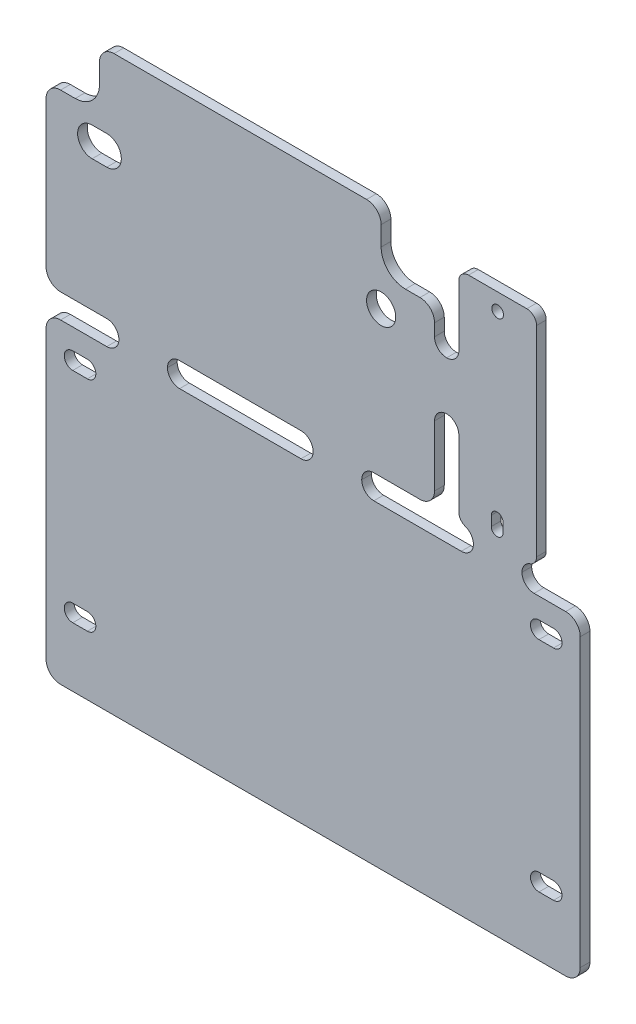
SolidWorks part; units mm, degrees
ref_plane "正面" through (0, 0, 0) normal (0, 0, 1) x (1, 0, 0)
ref_plane "平面" through (0, 0, 0) normal (0, 1, 0) x (1, 0, 0)
ref_plane "右側面" through (0, 0, 0) normal (1, 0, 0) x (0, 0, -1)
sketch "ｽｹｯﾁ1" plane through (0, 0, 0) normal (0, 0, 1) x (1, 0, 0)
  line L0 (-49.5, 24.75) -> (-46.5, 24.75)
  line L1 (55, 32.5) -> (-55, 32.5)
  line L2 (55, 32.5) -> (55, -32.5)
  line L3 (55, -32.5) -> (-55, -32.5)
  line L4 (-55, 32.5) -> (-55, -32.5)
  line L5 (55, 32.5) -> (-55, -32.5) construction
  line L6 (55, -32.5) -> (-55, 32.5) construction
  line L7 (-46.5, 28.25) -> (-49.5, 28.25)
  line L8 (-46.5, 28.25) -> (-46.5, 24.75) construction
  line L10 (-49.5, 28.25) -> (-49.5, 24.75) construction
  line L11 (-46.5, 28.25) -> (-49.5, 24.75) construction
  line L12 (-46.5, 24.75) -> (-49.5, 28.25) construction
  line L13 (-55, 4) -> (55, 4) construction
  line L14 (0, 32.5) -> (0, -32.5) construction
  line L15 (-46.5, -20.25) -> (-49.5, -20.25)
  line L16 (-49.5, -16.75) -> (-46.5, -16.75)
  line L17 (46.5, -20.25) -> (49.5, -20.25)
  line L18 (49.5, -16.75) -> (46.5, -16.75)
  line L19 (46.5, 28.25) -> (49.5, 28.25)
  line L20 (49.5, 24.75) -> (46.5, 24.75)
  arc A2 (-49.5, 28.25) -> (-49.5, 24.75) centre (-49.5, 26.5) ccw
  arc A3 (-46.5, 28.25) -> (-46.5, 24.75) centre (-46.5, 26.5) cw
  arc A4 (-49.5, -20.25) -> (-49.5, -16.75) centre (-49.5, -18.5) cw
  arc A5 (-46.5, -20.25) -> (-46.5, -16.75) centre (-46.5, -18.5) ccw
  arc A6 (46.5, -20.25) -> (46.5, -16.75) centre (46.5, -18.5) cw
  arc A7 (49.5, -20.25) -> (49.5, -16.75) centre (49.5, -18.5) ccw
  arc A8 (49.5, 28.25) -> (49.5, 24.75) centre (49.5, 26.5) cw
  arc A9 (46.5, 28.25) -> (46.5, 24.75) centre (46.5, 26.5) ccw
  point P0 (0, 0)
  point P6 (-48, 26.5)
  dimension "D3" = 3.5
  dimension "D4" = 3
  dimension "D1" = 65
  dimension "D2" = 110
  dimension "D5" = 6
  dimension "D6" = 7
  dimension "D7" = 22.5
extrude "ﾎﾞｽ - 押し出し1" add sketch "ｽｹｯﾁ1" along normal blind 2
fillet "ﾌｨﾚｯﾄ1" radius 3 4 edges at (55, 32.5, 1) (55, -32.5, 1) (-55, -32.5, 1) (-55, 32.5, 1)
sketch "ｽｹｯﾁ2" plane through (0, 0, 2) normal (0, 0, 1) x (1, 0, 0)
  line L0 (-45.5, 64.5) -> (-42.5, 64.5)
  line L2 (-55, 85.5) -> (-55, 37.5) construction
  line L3 (-55, 37.5) -> (25, 37.5) construction
  line L4 (25, 85.5) -> (25, 37.5) construction
  line L5 (-55, 85.5) -> (25, 37.5) construction
  line L6 (-55, 37.5) -> (25, 85.5) construction
  line L7 (-45.5, 70.5) -> (-42.5, 70.5)
  line L8 (-45.5, 70.5) -> (-45.5, 64.5) construction
  line L10 (-42.5, 70.5) -> (-42.5, 64.5) construction
  line L11 (-45.5, 70.5) -> (-42.5, 64.5) construction
  line L12 (-45.5, 64.5) -> (-42.5, 70.5) construction
  line L17 (-44, 67.5) -> (14, 67.5) construction
  line L18 (-15, 85.5) -> (-15, 37.5) construction
  line L24 (-55, 85.5) -> (25, 85.5) construction
  line L25 (-55, 37.5) -> (25, 37.5)
  line L26 (25, 37.5) -> (25, 73.5)
  line L27 (25, 73.5) -> (14, 73.5)
  line L28 (14, 73.5) -> (14, 85.5)
  line L29 (14, 85.5) -> (-44, 85.5)
  line L30 (-44, 73.5) -> (-44, 85.5)
  line L31 (-55, 73.5) -> (-44, 73.5)
  line L32 (-55, 37.5) -> (-55, 73.5)
  line L33 (-55, 29.5) -> (-55, -29.5) construction
  line L34 (52, 32.5) -> (-52, 32.5) construction
  arc A0 (-45.5, 70.5) -> (-45.5, 64.5) centre (-45.5, 67.5) ccw
  arc A1 (-42.5, 70.5) -> (-42.5, 64.5) centre (-42.5, 67.5) cw
  circle A2 centre (14, 67.5) radius 3
  point P0 (-15, 61.5)
  point P5 (-44, 67.5)
  point P20 (-14.6209, 73.2894)
  dimension "D6" = 6
  dimension "D7" = 29
  dimension "D1" = 80
  dimension "D2" = 48
  dimension "D3" = 6
  dimension "D4" = 3
  dimension "D5" = 29
  dimension "D8" = 12
  dimension "D9" = 11
  dimension "D10" = 18
  dimension "D11" = 5
extrude "ﾎﾞｽ - 押し出し2" add sketch "ｽｹｯﾁ2" against normal blind 2 separate body
fillet "ﾌｨﾚｯﾄ5" radius 3 6 edges at (-44, 85.5, 1) (-55, 73.5, 1) (14, 85.5, 1) (25, 73.5, 1) (25, 37.5, 1) (-55, 37.5, 1)
fillet "ﾌｨﾚｯﾄ6" radius 5 2 edges at (14, 73.5, 1) (-44, 73.5, 1)
sketch "ｽｹｯﾁ4" plane through (0, 0, 2) normal (0, 0, 1) x (1, 0, 0)
  line L0 (-40, 37.5) -> (-40, 32.5)
  line L1 (-52, 37.5) -> (22, 37.5) construction
  line L2 (52, 32.5) -> (-52, 32.5) construction
  line L3 (-40, 32.5) -> (-30, 32.5)
  line L4 (-30, 32.5) -> (-30, 37.5)
  line L5 (-30, 37.5) -> (-40, 37.5)
  line L6 (0, 37.5) -> (0, 32.5)
  line L7 (0, 32.5) -> (10, 32.5)
  line L8 (10, 32.5) -> (10, 37.5)
  line L9 (10, 37.5) -> (0, 37.5)
  line L10 (-55, 70.5) -> (-55, 40.5) construction
  line L11 (25, 40.5) -> (25, 70.5) construction
  dimension "D1" = 10
  dimension "D2" = 10
  dimension "D3" = 15
  dimension "D4" = 15
extrude "ﾎﾞｽ - 押し出し4" add sketch "ｽｹｯﾁ4" against normal blind 2
fillet "ﾌｨﾚｯﾄ7" radius 2.5 8 edges at (10, 37.5, 1) (10, 32.5, 1) (0, 37.5, 1) (0, 32.5, 1) (-30, 37.5, 1) (-30, 32.5, 1) (-40, 37.5, 1) (-40, 32.5, 1)
sketch "ｽｹｯﾁ5" plane through (0, 0, 2) normal (0, 0, 1) x (1, 0, 0)
  line L0 (36.6832, 42) -> (36.6832, 40)
  line L1 (30, 82.5) -> (46, 82.5)
  line L2 (30, 82.5) -> (30, 37.5)
  line L3 (30, 37.5) -> (46, 37.5)
  line L4 (46, 82.5) -> (46, 37.5)
  line L5 (30, 82.5) -> (46, 37.5) construction
  line L6 (30, 37.5) -> (46, 82.5) construction
  line L7 (39.0832, 42) -> (36.6832, 42) construction
  line L8 (39.0832, 42) -> (39.0832, 40)
  line L9 (39.0832, 40) -> (36.6832, 40) construction
  line L11 (39.0832, 42) -> (36.6832, 40) construction
  line L12 (39.0832, 40) -> (36.6832, 42) construction
  line L13 (25, 40.5) -> (25, 70.5) construction
  line L14 (52, 32.5) -> (12.5, 32.5) construction
  circle A0 centre (38, 79) radius 1.2
  arc A1 (36.6832, 42) -> (39.0832, 42) centre (37.8832, 42) cw
  arc A2 (39.0832, 40) -> (36.6832, 40) centre (37.8832, 40) cw
  point P0 (38, 60)
  point P7 (37.8832, 41)
  dimension "D3" = 2.4
  dimension "D1" = 45
  dimension "D2" = 16
  dimension "D4" = 2.4
  dimension "D5" = 2
  dimension "D6" = 19
  dimension "D7" = 19
  dimension "D8" = 5
  dimension "D9" = 5
extrude "ﾎﾞｽ - 押し出し5" add sketch "ｽｹｯﾁ5" against normal blind 2 separate body
sketch "ｽｹｯﾁ6" plane through (0, 0, 2) normal (0, 0, 1) x (1, 0, 0)
  line L0 (33, 37.5) -> (33, 32.5)
  line L1 (30, 37.5) -> (46, 37.5) construction
  line L2 (52, 32.5) -> (12.5, 32.5) construction
  line L3 (33, 32.5) -> (43, 32.5)
  line L4 (43, 32.5) -> (43, 37.5)
  line L5 (43, 37.5) -> (33, 37.5)
  line L6 (25, 65.5) -> (30, 65.5)
  line L7 (25, 40.5) -> (25, 70.5) construction
  line L8 (30, 82.5) -> (30, 37.5) construction
  line L9 (30, 65.5) -> (30, 55.5)
  line L10 (30, 55.5) -> (25, 55.5)
  line L11 (25, 55.5) -> (25, 65.5)
  line L13 (12.5, 37.5) -> (22, 37.5) construction
  dimension "D1" = 10
  dimension "D2" = 10
  dimension "D3" = 3
  dimension "D4" = 18
extrude "ﾎﾞｽ - 押し出し6" add sketch "ｽｹｯﾁ6" against normal blind 2
fillet "ﾌｨﾚｯﾄ8" radius 2.5 8 edges at (43, 32.5, 1) (43, 37.5, 1) (33, 32.5, 1) (33, 37.5, 1) (30, 55.5, 1) (25, 55.5, 1) (25, 65.5, 1) (30, 65.5, 1)
fillet "ﾌｨﾚｯﾄ9" radius 2 4 edges at (46, 82.5, 1) (30, 82.5, 1) (46, 37.5, 1) (30, 37.5, 1)
